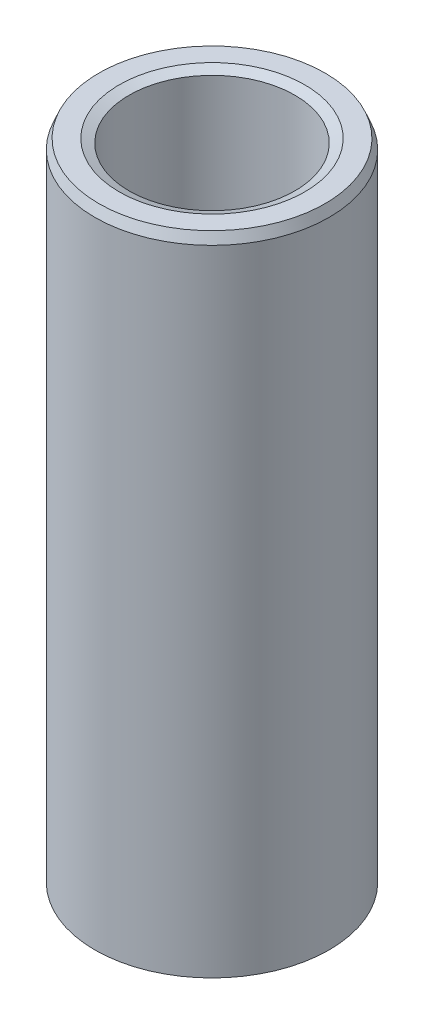
SolidWorks part; units mm, degrees
ref_plane "Front Plane" through (0, 0, 0) normal (0, 0, 1) x (1, 0, 0)
ref_plane "Top Plane" through (0, 0, 0) normal (0, 1, 0) x (1, 0, 0)
ref_plane "Right Plane" through (0, 0, 0) normal (1, 0, 0) x (0, 0, -1)
sketch "Sketch1" plane through (0, 0, 0) normal (0, 1, 0) x (1, 0, 0)
  circle A0 centre (0, 0) radius 32.5
  dimension "SLEEVE_OD" = 65
extrude "Boss-Extrude1" add sketch "Sketch1" along normal blind 179.8114
sketch "Sketch2" plane through (0, 0, 0) normal (0, 1, 0) x (1, 0, 0)
  circle A0 centre (0, 0) radius 23.0016
  dimension "BORE_D" = 46.0033
extrude "Cut-Extrude1" cut sketch "Sketch2" along normal through all
chamfer "Chamfer1" distance 2.7324 angle 22.407 4 edges at (0, 179.8114, 23.0016) (0, 0, 23.0016) (0, 0, 32.5) (0, 179.8114, 32.5) first distance on face at (0, 179.8114, 23.0016) first distance on face at (0, 0, 23.0016) first distance on face at (0, 179.8114, 32.5)
